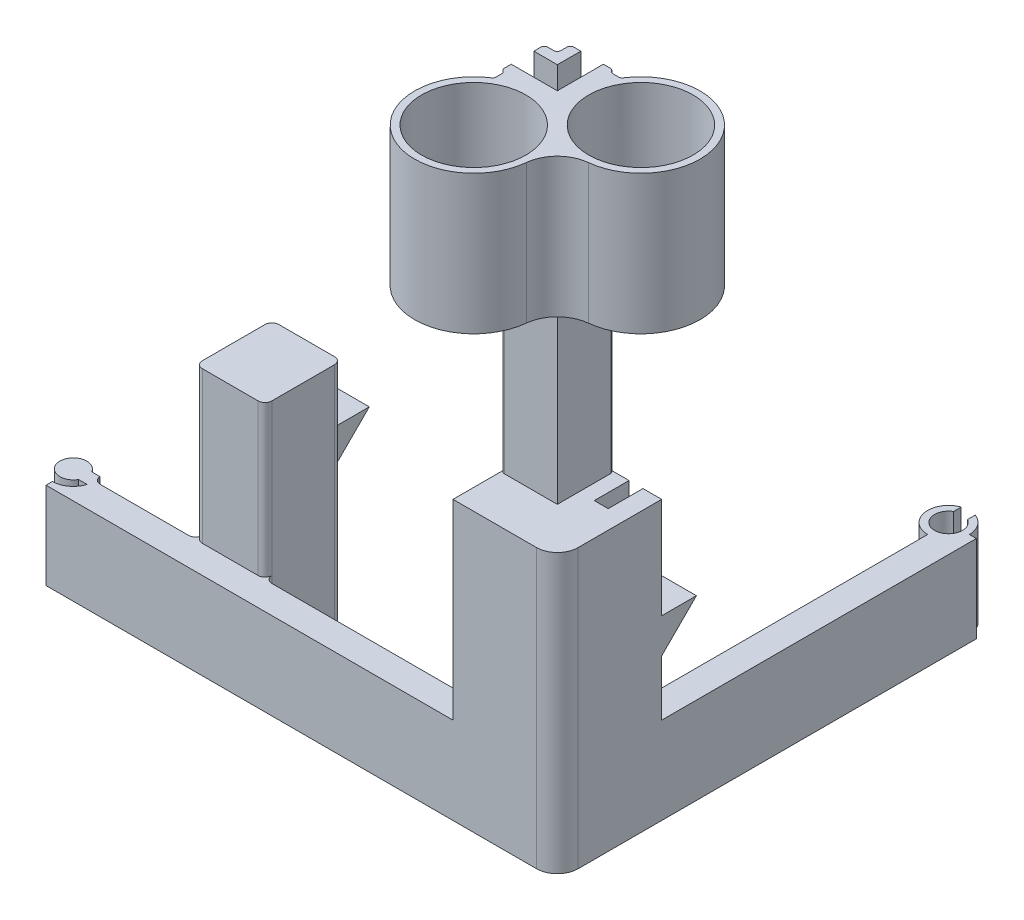
SolidWorks part; units mm, degrees
ref_plane "Front Plane" through (0, 0, 0) normal (0, 0, 1) x (1, 0, 0)
ref_plane "Top Plane" through (0, 0, 0) normal (0, 1, 0) x (1, 0, 0)
ref_plane "Right Plane" through (0, 0, 0) normal (1, 0, 0) x (0, 0, -1)
sketch "Sketch1" plane through (0, 0, 0) normal (0, 1, 0) x (1, 0, 0)
  line L1 (-15, -15) -> (15, -15)
  line L2 (-15, -15) -> (-15, 15)
  line L3 (-15, 15) -> (15, 15)
  line L4 (15, -15) -> (15, 15)
  line L5 (-15, -15) -> (15, 15) construction
  line L6 (-15, 15) -> (15, -15) construction
  point P0 (0, 0)
  dimension "D1" = 30
extrude "Boss-Extrude1" add sketch "Sketch1" along normal blind 80
sketch "Sketch2" plane through (0, 80, 0) normal (0, 1, 0) x (1, 0, 0)
  line L0 (-15, -15) -> (15, -15) construction
  line L1 (15, -15) -> (15, 15) construction
  circle A0 centre (9, -9) radius 6
  dimension "D1" = 12
extrude "Boss-Extrude2" add sketch "Sketch2" along normal blind 22
sketch "Sketch3" plane through (0, 80, 0) normal (0, 1, 0) x (1, 0, 0)
  line L2 (9, -15) -> (15, -15)
  line L4 (15, -15) -> (15, -9)
  circle A1 centre (9, -9) radius 6
  arc A4 (9, -15) -> (15, -9) centre (9, -9) ccw
  dimension "D1" = 0
extrude "Cut-Extrude1" cut sketch "Sketch3" against normal through all
sketch "Sketch4" plane through (0, 80, 0) normal (0, 1, 0) x (1, 0, 0)
  line L1 (-8.25, 11.25) -> (-1.75, 11.25) construction
  line L2 (-8.25, 11.25) -> (-8.25, 8.25)
  line L6 (-1.75, 1.75) -> (-11.25, 1.75)
  line L8 (-8.25, 8.25) -> (-11.25, 8.25)
  line L9 (-11.25, 1.75) -> (-11.25, 8.25) construction
  line L10 (-1.75, 11.25) -> (-1.75, 1.75)
  line L11 (-11.25, -1.25) -> (1.25, -1.25)
  line L12 (1.25, -1.25) -> (1.25, 11.25)
  line L13 (1.25, 11.25) -> (-1.75, 11.25) construction
  line L14 (-11.25, 1.75) -> (-11.25, -1.25) construction
  line L15 (-11.25, 8.25) -> (-11.25, 11.25) construction
  line L16 (-11.25, 11.25) -> (-8.25, 11.25) construction
  line L17 (1.25, 11.25) -> (1.25, 15)
  line L18 (15, 15) -> (-15, 15) construction
  line L19 (1.25, 15) -> (-1.75, 15)
  line L20 (-1.75, 15) -> (-1.75, 11.25)
  line L21 (-8.25, 11.25) -> (-8.25, 15)
  line L22 (-8.25, 15) -> (-11.25, 15)
  line L23 (-11.25, 15) -> (-11.25, 11.25)
  line L24 (-11.25, 11.25) -> (-15, 11.25)
  line L25 (-15, 15) -> (-15, -15) construction
  line L26 (-15, 11.25) -> (-15, 8.25)
  line L27 (-15, 8.25) -> (-11.25, 8.25)
  line L28 (-11.25, 1.75) -> (-15, 1.75)
  line L29 (-15, 1.75) -> (-15, -1.25)
  line L30 (-15, -1.25) -> (-11.25, -1.25)
  dimension "D1" = 6.5
  dimension "D2" = 3
  dimension "D3" = 3.75
extrude "Boss-Extrude3" add sketch "Sketch4" along normal blind 100
sketch "Sketch6" plane through (0, 0, 0) normal (0, -1, 0) x (1, 0, 0)
  line L1 (15, -15) -> (7, -15)
  line L2 (15, -15) -> (15, -105.5)
  line L3 (15, -105.5) -> (13, -105.5)
  line L4 (7, -15) -> (7, -99.5)
  arc A1 (7, -99.5) -> (13, -105.5) centre (7, -105.5) ccw
  dimension "D3" = 12
  dimension "D1" = 90.5
  dimension "D2" = 8
extrude "Boss-Extrude5" add sketch "Sketch6" against normal blind 2
sketch "Sketch7" plane through (0, 2, 0) normal (0, 1, 0) x (1, 0, 0)
  line L0 (7, 109.5) -> (7, 111.5) construction
  line L1 (9, 111.1569) -> (9, 108.9641)
  line L2 (5, 111.1569) -> (5, 108.9641)
  line L3 (7, 101.5) -> (7, 99.5) construction
  line L4 (15, 105.5) -> (13, 105.5)
  line L5 (15, 105.5) -> (15, 15)
  line L6 (15, 15) -> (7, 15)
  line L7 (7, 15) -> (7, 99.5) construction
  line L8 (15, 15) -> (1.25, 15) construction
  line L9 (7, 15) -> (7, 99.5)
  arc A0 (5, 111.1569) -> (7, 99.5) centre (7, 105.5) ccw
  arc A1 (13, 105.5) -> (7, 99.5) centre (7, 105.5) ccw construction
  arc A2 (5, 108.9641) -> (9, 108.9641) centre (7, 105.5) ccw
  arc A3 (13, 105.5) -> (9, 111.1569) centre (7, 105.5) ccw
  dimension "D1" = 2
  dimension "D2" = 2
extrude "Boss-Extrude6" add sketch "Sketch7" along normal offset from surface (23 mm away) 25 up to face at (3.75, 0, -38.4375)
sketch "Sketch9" plane through (0, 0, 0) normal (0, -1, 0) x (1, 0, 0)
  line L0 (15, -15) -> (7, -15) construction
  line L1 (-15, 15) -> (-132.175, 15) construction
  line L2 (-15, 15) -> (-15, 7)
  line L3 (-15, 7) -> (-126.175, 7) construction
  line L4 (-132.175, 15) -> (-132.175, 13.1746) construction
  line L5 (-136.05, 7) -> (-136.175, 7) construction
  line L6 (-128.175, 7) -> (-126.175, 7) construction
  line L7 (-126.175, 9) -> (-128.856, 9) construction
  line L8 (7, -109.5) -> (7, -111.5) construction
  line L9 (9, -111.1569) -> (5, -111.1569) construction
  line L10 (-126.175, 5) -> (-128.856, 5) construction
  line L11 (-126.175, 9) -> (-126.175, 5) construction
  line L12 (-128.7978, 8.9) -> (-126.3, 8.9)
  line L13 (-128.7978, 5.1) -> (-126.175, 5.1) construction
  line L14 (-126.175, 5.1) -> (-126.175, 7) construction
  line L15 (-126.175, 8.9) -> (-126.3, 8.9) construction
  line L16 (-132.05, 15) -> (-132.05, 13.1733)
  line L17 (-132.05, 14.0867) -> (-132.175, 14.0873) construction
  line L18 (-132.05, 15) -> (-15, 15)
  line L19 (-126.175, 5.1) -> (-126.175, 7) construction
  line L20 (-15, 7) -> (-126.175, 7)
  line L21 (-126.4838, 5.1) -> (-128.7978, 5.1)
  circle A0 centre (-132.175, 7) radius 4 construction
  arc A1 (9, -108.9641) -> (5, -108.9641) centre (7, -105.5) ccw construction
  arc A2 (-128.7978, 8.9) -> (-128.7978, 5.1) centre (-132.175, 7) ccw
  arc A4 (-126.3, 8.9) -> (-132.175, 13.1746) centre (-132.175, 7) ccw construction
  arc A6 (-126.3, 8.9) -> (-132.05, 13.1733) centre (-132.175, 7) ccw
  arc A7 (-126.4838, 5.1) -> (-126.175, 7) centre (-132.175, 7) ccw
  arc A8 (7, -99.5) -> (5, -111.1569) centre (7, -105.5) ccw construction
  dimension "D1" = 117.175
  dimension "D2" = 0.125
  dimension "D3" = 1.9
extrude "Boss-Extrude7" add sketch "Sketch9" against normal blind 25
fillet "Fillet1" radius 2 1 edges at (-126.175, 12.5, 7)
sketch "Sketch11" plane through (0, 0, 0) normal (0, -1, 0) x (1, 0, 0)
  line L0 (-126.3, 8.9) -> (-126.425, 8.9) construction
  line L2 (-126.3, 8.9) -> (-128.7978, 8.9) construction
  line L3 (-136.05, 7) -> (-136.175, 7) construction
  circle A0 centre (-132.175, 7) radius 6.0558
  arc A5 (-128.7978, 8.9) -> (-128.7978, 5.1) centre (-132.175, 7) ccw construction
extrude "Cut-Extrude2" cut sketch "Sketch11" against normal offset from surface (2.125 mm away) 0.125 up to face at (7, 2, -108.2802) offset beyond the face yes
sketch "Sketch12" plane through (-15, 0, 0) normal (-1, 0, 0) x (0, 0, 1)
  line L1 (-15, 77) -> (-1.75, 77)
  line L2 (-15, 77) -> (-15, 68.5)
  line L3 (-15, 68.5) -> (-1.75, 68.5)
  line L4 (-1.75, 77) -> (-1.75, 68.5)
  line L6 (-15, 80) -> (-15, 0) construction
  line L7 (-15, 80) -> (-1.75, 80) construction
  line L9 (-1.75, 180) -> (-1.75, 80) construction
  dimension "D1" = 8.5
  dimension "D2" = 3
extrude "Cut-Extrude4" cut sketch "Sketch12" against normal up to surface (13.25 mm away) up to face at (-1.75, 130, -8.375)
sketch "Sketch14" plane through (0, 0, 15) normal (0, 0, 1) x (1, 0, 0)
  line L0 (15, 0) -> (-136.05, 0) construction
  line L1 (-136.05, 25) -> (-136.05, 2.125) construction
  line L2 (-132.05, 0) -> (9, 0) construction
sketch "Sketch15" plane through (0, 80, 0) normal (0, 1, 0) x (1, 0, 0)
  line L4 (-11.25, 11.25) -> (-11.25, 15)
  line L5 (-11.25, 15) -> (-15, 15)
  line L6 (-15, 15) -> (-15, 11.25)
  line L7 (-15, 11.25) -> (-11.25, 11.25)
  line L8 (-11.25, 11.25) -> (-11.25, 15)
  line L9 (-11.25, 15) -> (-15, 15)
  line L10 (-15, 15) -> (-15, 11.25)
  line L11 (-15, 11.25) -> (-11.25, 11.25)
  dimension "D1" = 0
extrude "Cut-Extrude5" cut sketch "Sketch15" against normal up to next
fillet "Fillet2" radius 1 5 edges at (1.25, 130, -15) (-11.25, 128.5, -15) (-11.25, 128.5, -11.25) (-15, 128.5, -11.25) (-15, 130, 1.25)
sketch "Sketch16" plane through (0, 80, 0) normal (0, 1, 0) x (1, 0, 0)
  circle A0 centre (9, -9) radius 6
  circle A1 centre (9, -9) radius 6 construction
extrude "Cut-Extrude7" cut sketch "Sketch16" along normal up to next
sketch "Sketch17" plane through (0, 180, 0) normal (0, 1, 0) x (1, 0, 0)
  line L0 (18.7916, -9.75) -> (18.7916, -11.75) construction
  line L1 (1.25, 5.25) -> (3.7916, 5.25) construction
  line L2 (1.25, -1.25) -> (1.25, 14) construction
  line L3 (-5.25, -3.7916) -> (-5.25, -1.25) construction
  line L4 (-14, -1.25) -> (1.25, -1.25) construction
  line L6 (-5.25, -1.25) -> (1.25, -1.25) construction
  line L7 (1.25, -1.25) -> (1.25, 5.25) construction
  line L8 (-14, -1.25) -> (-14, -4.2164)
  line L9 (1.25, 14) -> (4.2164, 14)
  line L10 (-14, -1.25) -> (1.25, -1.25)
  line L11 (1.25, -1.25) -> (1.25, 14)
  circle A0 centre (18.7916, 5.25) radius 15
  circle A1 centre (-5.25, -18.7916) radius 15
  arc A2 (20.5619, -11.6576) -> (4.2164, 14) centre (18.7916, 5.25) ccw
  arc A3 (-14, -4.2164) -> (11.6576, -20.5619) centre (-5.25, -18.7916) ccw
  arc A4 (11.6576, -20.5619) -> (20.5619, -11.6576) centre (21.6032, -21.6032) cw
  dimension "D1" = 30
  dimension "D3" = 10
  dimension "D2" = 2
  dimension "D4" = 6.5
extrude "Boss-Extrude8" add sketch "Sketch17" against normal blind 40
fillet "Fillet3" radius 1 4 edges at (4.2164, 160, -14) (1.25, 160, -14) (-14, 160, 1.25) (-14, 160, 4.2164)
sketch "Sketch18" plane through (0, 140, 0) normal (0, -1, 0) x (1, 0, 0)
  circle A0 centre (-5.25, 18.7916) radius 15 construction
  circle A1 centre (-5.25, 18.7916) radius 15
  circle A2 centre (-5.25, 18.7916) radius 7.5
  dimension "D1" = 15
extrude "Boss-Extrude9" add sketch "Sketch18" against normal blind 2
sketch "Sketch19" plane through (0, 140, 0) normal (0, -1, 0) x (1, 0, 0)
  line L0 (-5.25, 26.2916) -> (-5.25, 11.2916) construction
  circle A0 centre (-5.25, 18.7916) radius 7.5 construction
ref_plane "Plane1" through (-5.25, 0, 0) normal (-1, 0, 0) x (0, 0, -1)
sketch "Sketch21" plane through (-5.25, 0, 0) normal (-1, 0, 0) x (0, 0, -1)
  line L0 (-11.2916, -142) -> (-3.7916, -154.5)
  line L1 (-26.2916, -142) -> (-11.2916, -142) construction
  line L2 (-3.7916, -154.5) -> (-3.7916, -142)
  line L3 (-33.7916, -142) -> (-3.7916, -142) construction
  line L4 (-3.7916, -142) -> (-11.2916, -142)
  line L5 (-18.7916, -1065) -> (-18.7916, 48935) construction
  line L6 (-26.2916, -140) -> (-11.2916, -140) construction
  point P14 (-18.7916, -140)
  dimension "D1" = 12.5
revolve "Revolve1" add sketch "Sketch21" angle 360 about L5
ref_plane "Plane2" through (0, 0, 0) normal (0.7071, 0, -0.7071) x (-0.7071, 0, -0.7071)
mirror "Mirror1" about plane through (0, 0, 0) normal (0.7071, 0, -0.7071) of "Revolve1", "Boss-Extrude9"
sketch "Sketch22" plane through (0, 80, 0) normal (0, 1, 0) x (1, 0, 0)
  line L1 (5.625, 15) -> (9.625, 15)
  line L2 (5.625, 15) -> (5.625, 5)
  line L3 (5.625, 5) -> (9.625, 5)
  line L4 (9.625, 15) -> (9.625, 5)
  line L5 (15, 15) -> (0.25, 15) construction
  point P6 (7.625, 15)
  point P7 (7.625, 15)
  dimension "D1" = 4
  dimension "D2" = 10
extrude "Cut-Extrude8" cut sketch "Sketch22" against normal blind 25
sketch "Sketch23" plane through (0, 0, 0) normal (0, -1, 0) x (1, 0, 0)
  line L0 (-124.429, 7) -> (-15, 7) construction
  line L1 (-97.0718, 7) -> (-77.0718, 7)
  line L2 (-97.0718, 7) -> (-97.0718, -15)
  line L3 (-97.0718, -15) -> (-77.0718, -15)
  line L4 (-77.0718, 7) -> (-77.0718, -15)
  line L5 (7, -15) -> (-15, -15) construction
  line L6 (-124.429, 7) -> (-69.7145, 7) construction
  point P11 (-97.0718, 7)
  dimension "D1" = 20
extrude "Boss-Extrude10" add sketch "Sketch23" against normal up to surface (68.5 mm away) up to face at (-8.375, 68.5, -8.375)
sketch "Sketch24" plane through (0, 0, 0) normal (0, -1, 0) x (1, 0, 0)
  line L0 (-97.0718, 7) -> (-77.0718, 7) construction
  line L1 (-94.5718, -12.5) -> (-79.5718, -12.5)
  line L2 (-94.5718, -12.5) -> (-94.5718, 4.5)
  line L3 (-94.5718, 4.5) -> (-79.5718, 4.5)
  line L4 (-79.5718, -12.5) -> (-79.5718, 4.5)
  line L5 (-87.0718, 7) -> (-87.0718, 4.5) construction
  line L6 (-97.0718, -4) -> (-94.5718, -4) construction
  line L7 (-97.0718, 7) -> (-97.0718, -15) construction
  dimension "D1" = 2.5
extrude "Cut-Extrude9" cut sketch "Sketch24" against normal offset from surface (66 mm away) 2.5 up to face at (-87.0718, 68.5, -4)
fillet "Fillet4" radius 2 4 edges at (-97.0718, 12.5, 7) (-77.0718, 12.5, 7) (-77.0718, 34.25, -15) (-97.0718, 34.25, -15)
fillet "Fillet5" radius 2 2 edges at (-77.0718, 46.75, 7) (-97.0718, 46.75, 7)
chamfer "Chamfer1" distance 7 angle 45 4 edges at (-87.0718, 66, 4.5) (-79.5718, 66, -4) (-87.0718, 66, -12.5) (-94.5718, 66, -4)
sketch "Sketch25" plane through (0, 0, 0) normal (0, -1, 0) x (1, 0, 0)
  line L0 (-136.05, 7) -> (35.7916, 7) construction
  line L1 (35.7916, -111.5) -> (35.7916, 35.7916) construction
  line L2 (-5.25, 35.7916) -> (35.7916, 35.7916) construction
  line L3 (7, -111.5) -> (35.7916, -111.5) construction
  line L4 (13, -105.5) -> (1, -105.5) construction
  arc A1 (-128.7978, 8.9) -> (-128.7978, 5.1) centre (-132.175, 7) ccw construction
  arc A2 (4.5015, -14.4583) -> (20.5619, 11.6576) centre (18.7916, -5.25) ccw construction
  arc A3 (11.6576, 20.5619) -> (-14.4583, 4.5015) centre (-5.25, 18.7916) ccw construction
  arc A4 (7, -99.5) -> (13, -105.5) centre (7, -105.5) ccw construction
  point P3 (7, -105.5)
sketch "Sketch26" plane through (15, 0, 0) normal (1, 0, 0) x (0, 0, -1)
  line L0 (15, 55) -> (5, 55) construction
  line L1 (15, 55) -> (5, 55) construction
  line L2 (15, 55) -> (15, 51) construction
  line L3 (15, 80) -> (15, 25) construction
  line L4 (15, 51) -> (25, 51)
  line L5 (25, 51) -> (15, 41)
  line L6 (15, 41) -> (15, 51)
  dimension "D1" = 4
  dimension "D2" = 10
extrude "Boss-Extrude11" add sketch "Sketch26" against normal up to surface (30 mm away) up to face at (-15, 86.3125, -1.8438)
ref_plane "Plane3" through (-87.0718, 0, 0) normal (-1, 0, 0) x (0, 0, 1)
sketch "Sketch27" plane through (-87.0718, 0, 0) normal (-1, 0, 0) x (0, 0, 1)
  line L3 (-15, 51) -> (-25, 51)
  line L4 (-25, 51) -> (-15, 41)
  line L5 (-15, 41) -> (-15, 51)
  line L6 (-15, 51) -> (-25, 51)
  line L7 (-25, 51) -> (-15, 41)
  line L8 (-15, 41) -> (-15, 51)
  dimension "D1" = 0
extrude "Boss-Extrude12" add sketch "Sketch27" against normal up to vertex and the other way up to vertex up to point (-79.0718, 68.5, -15) other way up to point (-95.0718, 68.5, -15)
